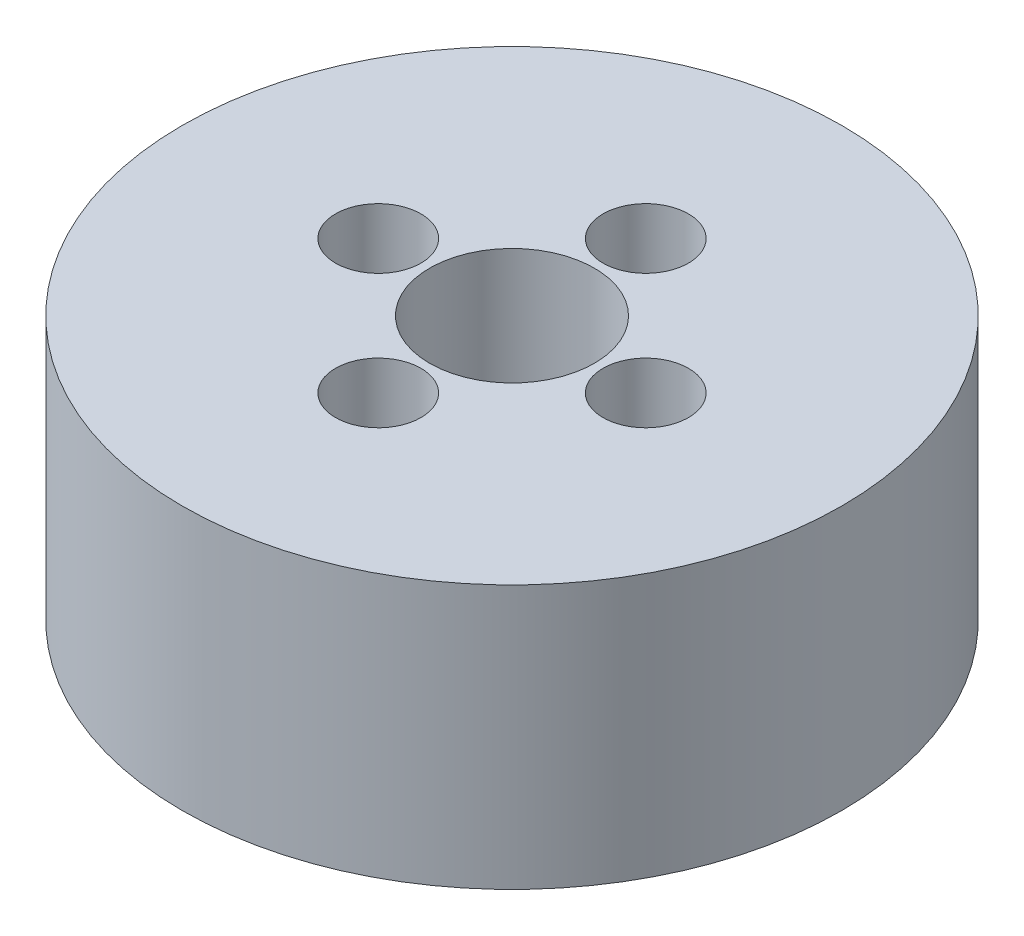
SolidWorks part; units mm, degrees
ref_plane "Front Plane" through (0, 0, 0) normal (0, 0, 1) x (1, 0, 0)
ref_plane "Top Plane" through (0, 0, 0) normal (0, 1, 0) x (1, 0, 0)
ref_plane "Right Plane" through (0, 0, 0) normal (1, 0, 0) x (0, 0, -1)
sketch "Sketch1" plane through (0, 0, 0) normal (0, 1, 0) x (1, 0, 0)
  circle A0 centre (0, 0) radius 30
  dimension "FLANGE_OD" = 60
extrude "Boss-Extrude1" add sketch "Sketch1" along normal blind 24
sketch "Sketch2" plane through (0, 0, 0) normal (0, 1, 0) x (1, 0, 0)
  circle A0 centre (0, 0) radius 7.5
  dimension "BORE_D" = 15
extrude "Cut-Extrude1" cut sketch "Sketch2" along normal through all
sketch "Sketch3" plane through (0, 24, 0) normal (0, 1, 0) x (1, 0, 0)
  circle A0 centre (0, 0) radius 12.1705 construction
  circle A1 centre (-12.1705, 0) radius 3.8873
  dimension "BOLT_D" = 7.7747
  dimension "BOLT_PCD" = 24.341
extrude "Cut-Extrude2" cut sketch "Sketch3" against normal blind 22.0155
pattern_circular "CirPattern1" count 4 over 360 about axis through (0, 0, 0) along (0, 1, 0) of "Cut-Extrude2"
